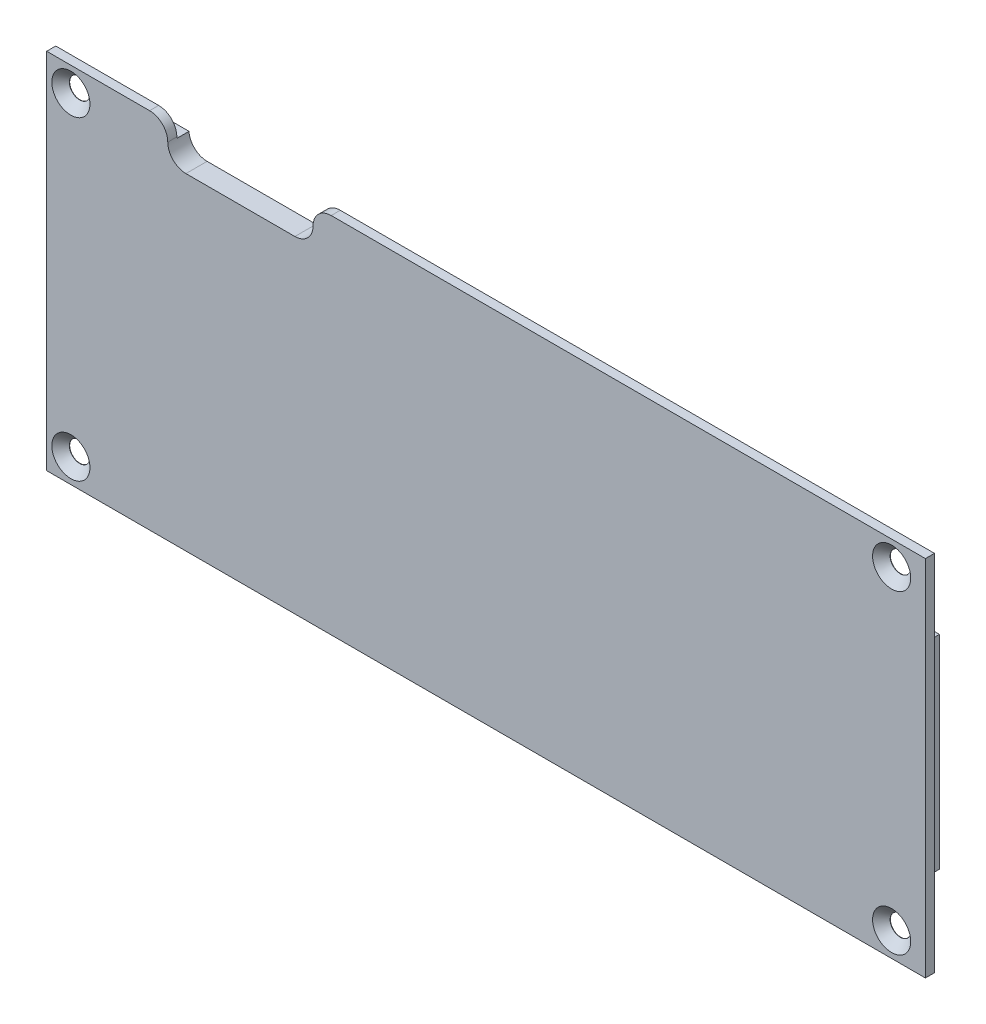
SolidWorks part; units mm, degrees
ref_plane "Plan de face" through (0, 0, 0) normal (0, 0, 1) x (1, 0, 0)
ref_plane "Plan de dessus" through (0, 0, 0) normal (0, 1, 0) x (1, 0, 0)
ref_plane "Plan de droite" through (0, 0, 0) normal (1, 0, 0) x (0, 0, -1)
sketch "Esquisse1" plane through (0, 0, 0) normal (0, 0, 1) x (1, 0, 0)
  line L1 (72.5741, -30) -> (-72.5741, -30)
  line L2 (72.5741, -30) -> (72.5741, 30)
  line L3 (72.5741, 30) -> (-72.5741, 30)
  line L4 (-72.5741, -30) -> (-72.5741, 30)
  line L5 (72.5741, -30) -> (-72.5741, 30) construction
  line L6 (72.5741, 30) -> (-72.5741, -30) construction
  point P0 (0, 0)
  dimension "D1" = 60
  dimension "D2" = 145.1482
extrude "Boss.-Extru.1" add sketch "Esquisse1" along normal blind 1.5
sketch "Esquisse2" plane through (0, 0, 0) normal (0, 0, -1) x (-1, 0, 0)
  line L0 (-71.3741, -16.8) -> (-71.3741, 16.8)
  line L1 (-61.3741, 26.8) -> (61.3741, 26.8)
  line L2 (71.3741, 16.8) -> (71.3741, -16.8)
  line L3 (61.3741, -26.8) -> (-61.3741, -26.8)
  line L4 (-72.5741, 30) -> (72.5741, 30) construction
  line L5 (72.5741, -30) -> (-72.5741, -30) construction
  line L6 (-72.5741, -30) -> (-72.5741, 30) construction
  line L7 (72.5741, 30) -> (72.5741, -30) construction
  arc A0 (-71.3741, 16.8) -> (-61.3741, 26.8) centre (-71.3741, 26.8) ccw
  arc A1 (-71.3741, -16.8) -> (-61.3741, -26.8) centre (-71.3741, -26.8) cw
  arc A2 (71.3741, -16.8) -> (61.3741, -26.8) centre (71.3741, -26.8) ccw
  arc A3 (61.3741, 26.8) -> (71.3741, 16.8) centre (71.3741, 26.8) ccw
  point P8 (-71.3741, 0)
  point P9 (71.3741, 0)
  point P11 (0, -26.8)
  point P12 (0, 26.8)
  dimension "D5" = 10
  dimension "D1" = 3.2
  dimension "D2" = 3.2
  dimension "D3" = 1.2
  dimension "D4" = 1.2
extrude "Boss.-Extru.2" add sketch "Esquisse2" along normal blind 2
sketch "Esquisse4" plane through (0, 0, 1.5) normal (0, 0, 1) x (1, 0, 0)
  line L0 (-68.5741, 26) -> (-68.5741, 30) construction
  line L1 (-68.5741, 26) -> (66.9981, 26)
  line L2 (-68.5741, 26) -> (-68.5741, -26)
  line L3 (-68.5741, -26) -> (66.9981, -26)
  line L4 (66.9981, 26) -> (66.9981, -26)
  line L5 (72.5741, 30) -> (-72.5741, 30) construction
  line L6 (-68.5741, -26) -> (-68.5741, -30) construction
  line L7 (-72.5741, -30) -> (72.5741, -30) construction
  line L8 (-72.5741, 30) -> (-72.5741, -30) construction
  line L9 (72.5741, -30) -> (72.5741, 30) construction
  dimension "D1" = 4
  dimension "D2" = 4
  dimension "D3" = 5.576
hole_wizard "Fraisage pour vis à tête fraisée M31" positions "Esquisse3D1" profile "Esquisse5" countersink size "M3" standard "ISO" end condition up to next
sketch3d "Esquisse3D1"
  point P0 (-68.5741, 26, 1.5)
  point P3 (-68.5741, -26, 1.5)
  point P6 (66.9981, 26, 1.5)
  point P9 (66.9981, -26, 1.5)
sketch "Esquisse5" plane through (-68.5741, 26, 1.5) normal (1, 0, 0) x (0, -1, 0)
  line L0 (0, 0) -> (0, 1.5)
  line L1 (0, 1.5) -> (1.7, 1.5)
  line L2 (1.7, 1.5) -> (1.7, 1.45)
  line L3 (1.7, 1.45) -> (3.15, 0)
  line L5 (3.15, 0) -> (0, 0)
  line L6 (-1.7, 1.45) -> (-3.15, 0) construction
  line L11 (0, -6.35) -> (0, 107.95) construction
  dimension "Diamètre du perçage jusqu'au prochain" = 3.4
  dimension "Profondeur du perçage jusqu'au prochain" = 1.5
  dimension "Diamètre du fraisage entrant" = 6.3
  dimension "Angle du fraisage entrant" = 90
sketch "Esquisse6" plane through (0, 0, 1.5) normal (0, 0, 1) x (1, 0, 0)
  line L0 (72.5741, 30) -> (-72.5741, 30) construction
  line L1 (-52.5741, 30) -> (-28.5741, 30)
  line L2 (-52.5741, 30) -> (-52.5741, 24)
  line L3 (-52.5741, 24) -> (-28.5741, 24)
  line L4 (-28.5741, 30) -> (-28.5741, 24)
  line L5 (-72.5741, 30) -> (-72.5741, -30) construction
  dimension "D1" = 6
  dimension "D2" = 24
  dimension "D3" = 20
extrude "Enlèv. mat.-Extru.1" cut sketch "Esquisse6" against normal through all both
fillet "Congé1" radius 3 4 edges at (-28.5741, 30, 0.75) (-28.5741, 24, -0.25) (-52.5741, 30, 0.75) (-52.5741, 24, -0.25)
sketch "Esquisse7" plane through (0, 0, -2) normal (0, 0, -1) x (-1, 0, 0)
  line L0 (28.5808, 26.8) -> (-61.3741, 26.8) construction
  line L1 (-35.9559, 26.8) -> (9.0441, 26.8)
  line L2 (-35.9559, 26.8) -> (-35.9559, -13.2)
  line L3 (-35.9559, -13.2) -> (9.0441, -13.2)
  line L4 (9.0441, 26.8) -> (9.0441, -13.2)
  line L6 (71.3741, -16.8) -> (71.3741, 16.8) construction
  dimension "D1" = 40
  dimension "D2" = 45
  dimension "D3" = 62.33
extrude "Enlèv. mat.-Extru.2" cut sketch "Esquisse7" against normal up to surface (2 mm away) up to face at (-66.8741, 26, 0)
